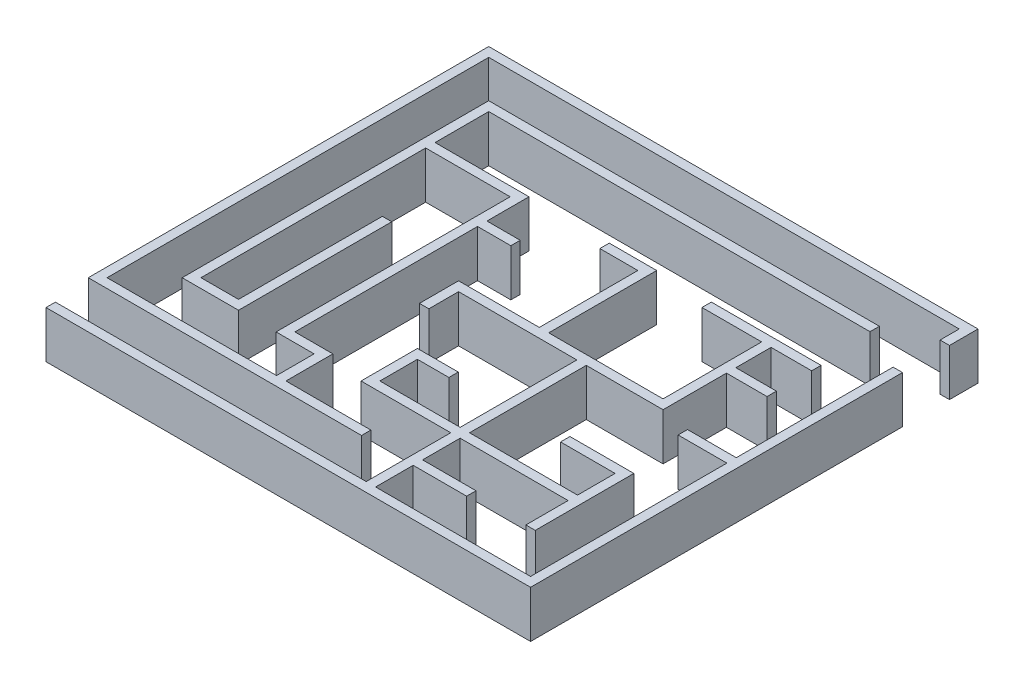
SolidWorks part; units mm, degrees
ref_plane "Front Plane" through (0, 0, 0) normal (0, 0, 1) x (1, 0, 0)
ref_plane "Top Plane" through (0, 0, 0) normal (0, 1, 0) x (1, 0, 0)
ref_plane "Right Plane" through (0, 0, 0) normal (1, 0, 0) x (0, 0, -1)
sketch "Sketch1" plane through (0, 0, 0) normal (0, 1, 0) x (1, 0, 0)
  line L0 (-2407.2669, -1690.1195) -> (2835.0391, -1690.1195)
  line L1 (2835.0391, -1690.1195) -> (2835.0391, 2333.7485)
  line L2 (-2407.2669, -1588.5195) -> (955.4391, -1588.5195)
  line L3 (2733.4391, -1588.5195) -> (2733.4391, 535.1745)
  line L4 (-2407.2669, -1588.5195) -> (-2407.2669, -1690.1195)
  line L5 (2733.4391, 2333.7485) -> (2835.0391, 2333.7485)
  line L6 (2733.4391, 535.1745) -> (2205.9624, 535.1745)
  line L7 (2733.4391, 636.7745) -> (2205.9624, 636.7745)
  line L8 (2205.9624, 636.7745) -> (2205.9624, 535.1745)
  line L9 (955.4391, -1588.5195) -> (955.4391, -674.1195)
  line L10 (1057.0391, -1588.5195) -> (1057.0391, -1182.1195)
  line L11 (1057.0391, -1182.1195) -> (1635.3971, -1182.1195)
  line L12 (1057.0391, -1080.5195) -> (1635.3971, -1080.5195)
  line L13 (1635.3971, -1080.5195) -> (1635.3971, -1182.1195)
  line L14 (2327.0391, -64.5195) -> (2327.0391, -1131.3195)
  line L15 (2225.4391, -166.1195) -> (1635.3971, -166.1195)
  line L16 (2327.0391, -64.5195) -> (1635.3971, -64.5195)
  line L17 (2225.4391, -166.1195) -> (2225.4391, -572.5195)
  line L18 (1635.3971, -64.5195) -> (1635.3971, -166.1195)
  line L19 (2225.4391, -1131.3195) -> (2327.0391, -1131.3195)
  line L20 (1057.0391, -674.1195) -> (2225.4391, -674.1195)
  line L21 (1057.0391, -572.5195) -> (2225.4391, -572.5195)
  line L22 (955.4391, -674.1195) -> (-14.8409, -674.1195)
  line L23 (-14.8409, -674.1195) -> (-14.8409, -64.5195)
  line L24 (-14.8409, -64.5195) -> (427.3731, -64.5195)
  line L25 (955.4391, -572.5195) -> (86.7591, -572.5195)
  line L26 (86.7591, -572.5195) -> (86.7591, -166.1195)
  line L27 (86.7591, -166.1195) -> (427.3731, -166.1195)
  line L28 (427.3731, -64.5195) -> (427.3731, -166.1195)
  line L29 (1057.0391, 690.3685) -> (1887.8731, 690.3685)
  line L30 (1887.8731, 690.3685) -> (1887.8731, 1376.1685)
  line L31 (1887.8731, 1376.1685) -> (2327.0391, 1376.1685)
  line L32 (1887.8731, 1477.7685) -> (2327.0391, 1477.7685)
  line L33 (2327.0391, 1477.7685) -> (2327.0391, 1376.1685)
  line L34 (1887.8731, 1858.7685) -> (2327.0391, 1858.7685)
  line L35 (1140.6051, 1960.1145) -> (2327.0391, 1960.3685)
  line L36 (2327.0391, 1960.3685) -> (2327.0391, 1858.7685)
  line L37 (955.4391, 690.3685) -> (-324.4669, 690.3685)
  line L38 (-324.4669, 690.3685) -> (-324.4669, 369.0585)
  line L39 (549.0391, 791.9685) -> (1786.2731, 791.9685)
  line L40 (-426.0669, 791.9685) -> (-426.0669, 369.0585)
  line L41 (-426.0669, 369.0585) -> (-324.4669, 369.0585)
  line L42 (1057.0391, -1080.5195) -> (1057.0391, -674.1195)
  line L43 (1786.2731, 791.9685) -> (1786.2731, 1858.7685)
  line L44 (498.2391, -1182.1195) -> (-2458.0669, -1182.1195)
  line L45 (-2458.0669, -1182.1195) -> (-2458.0669, 3150.3585)
  line L46 (-2458.0669, 3150.3585) -> (2835.0391, 3150.3585)
  line L47 (955.4391, 791.9685) -> (-426.0669, 791.9685) construction
  line L48 (447.4391, 791.9685) -> (447.4391, 1858.5145)
  line L49 (447.4391, 1858.5145) -> (35.9591, 1858.5145)
  line L50 (549.0391, 791.9685) -> (549.0391, 1960.1145)
  line L51 (549.0391, 1960.1145) -> (35.9591, 1960.1145)
  line L52 (35.9591, 1960.1145) -> (35.9591, 1858.5145)
  line L53 (2835.0391, 3150.3585) -> (2835.0391, 2841.7485)
  line L54 (1786.2731, 1858.7685) -> (1140.6051, 1858.7685)
  line L55 (1140.6051, 1858.7685) -> (1140.6051, 1960.1145)
  line L56 (955.4391, -1588.5195) -> (955.4391, 1618.7091) construction
  line L57 (498.2391, -1080.5195) -> (-421.2409, -1080.5195)
  line L58 (447.4391, 791.9685) -> (-426.0669, 791.9685)
  line L59 (1057.0391, -1588.5195) -> (1057.0391, 1618.7091) construction
  line L60 (2733.4391, 636.7745) -> (2733.4391, 2333.7485)
  line L61 (2733.4391, -1588.5195) -> (2733.4391, 2333.7485) construction
  line L62 (1887.8731, 1477.7685) -> (1887.8731, 1858.7685)
  line L63 (-2356.4669, -1080.5195) -> (-2356.4669, 3048.7585)
  line L64 (2225.4391, -674.1195) -> (2225.4391, -1131.3195)
  line L65 (2225.4391, -166.1195) -> (2225.4391, -1131.3195) construction
  line L66 (955.4391, -572.5195) -> (955.4391, 690.3685)
  line L67 (1057.0391, -572.5195) -> (1057.0391, 690.3685)
  line L68 (1057.0391, -1588.5195) -> (2733.4391, -1588.5195)
  line L69 (-2407.2669, -1588.5195) -> (2733.4391, -1588.5195) construction
  line L70 (-2356.4669, 3048.7585) -> (2733.4391, 3048.7585)
  line L71 (2733.4391, 3048.7585) -> (2733.4391, 2841.7485)
  line L72 (2733.4391, 2841.7485) -> (2835.0391, 2841.7485)
  line L73 (498.2391, -1080.5195) -> (498.2391, -1182.1195)
  line L74 (-421.2409, -572.5195) -> (-421.2409, -1080.5195)
  line L75 (-421.2409, -572.5195) -> (-832.4669, -572.5195)
  line L76 (-832.4669, -572.5195) -> (-832.4669, 1403.6005)
  line L77 (-832.4669, 1403.6005) -> (-472.0409, 1403.6005)
  line L78 (-472.0409, 1403.6005) -> (-472.0409, 1505.2005)
  line L79 (-472.0409, 1505.2005) -> (-832.4669, 1505.2005)
  line L80 (-832.4669, 1505.2005) -> (-832.4669, 1960.1145)
  line L81 (-522.8409, -674.1195) -> (-522.8409, -1080.5195)
  line L82 (-522.8409, -674.1195) -> (-934.0669, -674.1195)
  line L83 (-934.0669, -674.1195) -> (-934.0669, 1454.4005)
  line L84 (-934.0669, 1454.4005) -> (-934.0669, 1454.4005)
  line L85 (-934.0669, 1454.4005) -> (-934.0669, 1454.4005)
  line L86 (-934.0669, 1454.4005) -> (-934.0669, 1454.4005)
  line L87 (-934.0669, 1454.4005) -> (-934.0669, 1858.5145)
  line L88 (-832.4669, 1960.1145) -> (-1848.4669, 1960.1145)
  line L89 (-934.0669, 1858.5145) -> (-1848.4669, 1858.5145)
  line L90 (-1848.4669, 1858.5145) -> (-1848.4669, -572.5195)
  line L91 (-1848.4669, -572.5195) -> (-1442.0669, -572.5195)
  line L92 (-1442.0669, -572.5195) -> (-1442.0669, 983.9925)
  line L93 (-421.2409, -572.5195) -> (-421.2409, -1080.5195)
  line L94 (-421.2409, -572.5195) -> (-832.4669, -572.5195)
  line L95 (-832.4669, -572.5195) -> (-832.4669, 1454.4005)
  line L96 (-832.4669, 1454.4005) -> (-832.4669, 1454.4005)
  line L97 (-832.4669, 1454.4005) -> (-832.4669, 1454.4005)
  line L98 (-832.4669, 1454.4005) -> (-832.4669, 1454.4005)
  line L99 (-832.4669, 1454.4005) -> (-832.4669, 1960.1145)
  line L100 (-1848.4669, 1960.1145) -> (-1848.4669, 2540.7585)
  line L101 (-1848.4669, 2540.7585) -> (2276.2391, 2540.7585)
  line L102 (-1950.0669, -674.1195) -> (-1340.4669, -674.1195)
  line L103 (-1340.4669, -674.1195) -> (-1340.4669, 983.9925)
  line L104 (-1442.0669, 983.9925) -> (-1340.4669, 983.9925)
  line L105 (-1950.0669, 1960.1145) -> (-1950.0669, -674.1195) construction
  line L106 (-832.4669, 1960.1145) -> (-1950.0669, 1960.1145) construction
  line L107 (-1950.0669, -674.1195) -> (-1950.0669, 2642.3585)
  line L108 (2276.2391, 2540.7585) -> (2276.2391, 2642.3585)
  line L109 (2276.2391, 2642.3585) -> (-1950.0669, 2642.3585)
  line L110 (-522.8409, -1080.5195) -> (-2356.4669, -1080.5195)
  line L111 (498.2391, -1080.5195) -> (-2356.4669, -1080.5195) construction
  point P8 (2469.7007, 535.1745)
  point P42 (2107.4561, 1376.1685)
  point P58 (955.4391, -1131.3195)
  dimension "D1" = 5242.306
  dimension "D2" = 4023.868
  dimension "D4" = 2123.694
  dimension "D6" = 3362.706
  dimension "D8" = 578.358
  dimension "D10" = 457.2
  dimension "D11" = 406.4
  dimension "D12" = 1066.8
  dimension "D14" = 691.642
  dimension "D15" = 406.4
  dimension "D17" = 970.28
  dimension "D18" = 442.214
  dimension "D20" = 1262.888
  dimension "D21" = 830.834
  dimension "D22" = 2956.306
  dimension "D23" = 685.8
  dimension "D25" = 381
  dimension "D27" = 1279.906
  dimension "D28" = 321.31
  dimension "D31" = 873.506
  dimension "D32" = 1066.546
  dimension "D33" = 411.48
  dimension "D35" = 645.668
  dimension "D26" = 457.2
  dimension "D30" = 406.4
  dimension "D36" = 4332.478
  dimension "D37" = 5293.106
  dimension "D38" = 308.61
  dimension "D40" = 919.48
  dimension "D41" = 508
  dimension "D42" = 411.226
  dimension "D43" = 1976.12
  dimension "D44" = 360.426
  dimension "D45" = 101.6
  dimension "D46" = 101.6
  dimension "D47" = 1016
  dimension "D48" = 2431.034
  dimension "D49" = 406.4
  dimension "D50" = 1556.512
  dimension "D52" = 580.644
  dimension "D53" = 4124.706
  dimension "D54" = 101.6
  dimension "D3" = 101.6
  dimension "D5" = 101.6
  dimension "D7" = 101.6
  dimension "D9" = 101.6
  dimension "D13" = 101.6
  dimension "D16" = 101.6
  dimension "D19" = 101.6
  dimension "D24" = 101.6
  dimension "D29" = 101.6
  dimension "D34" = 101.6
  dimension "D39" = 101.6
  dimension "D51" = 101.6
extrude "Boss-Extrude1" add sketch "Sketch1" along normal blind 508 contours L2 L9 L22 L23 L24 L28 L27 L26 L25 L66 L37 L38 L41 L40 L58 L48 L49 L52 L51 L50 L39 L43 L54 L55 L35 L36 L34 L62 L32 L33 L31 L30 L29 L67 L21 L17 L15 L18 L16 L14 L19 L64 L20 L42 L12 L13 L11 L10 L68 L3 L6 L8 L7 L60 L5 L1 L0 L4
extrude "Boss-Extrude2" add sketch "Sketch1<3>" along normal blind 508 separate body contours L45 L46 L53 L72 L71 L70 L63 L110 L81 L82 L83 L84 L85 L86 L87 L89 L90 L91 L92 L104 L103 L102 L107 L109 L108 L101 L100 L88 L80 L79 L78 L77 L76 L75 L74 L57 L73 L44
sketch "Sketch1<3>" plane through (0, 0, 0) normal (0, 1, 0) x (1, 0, 0) same geometry as "Sketch1"
